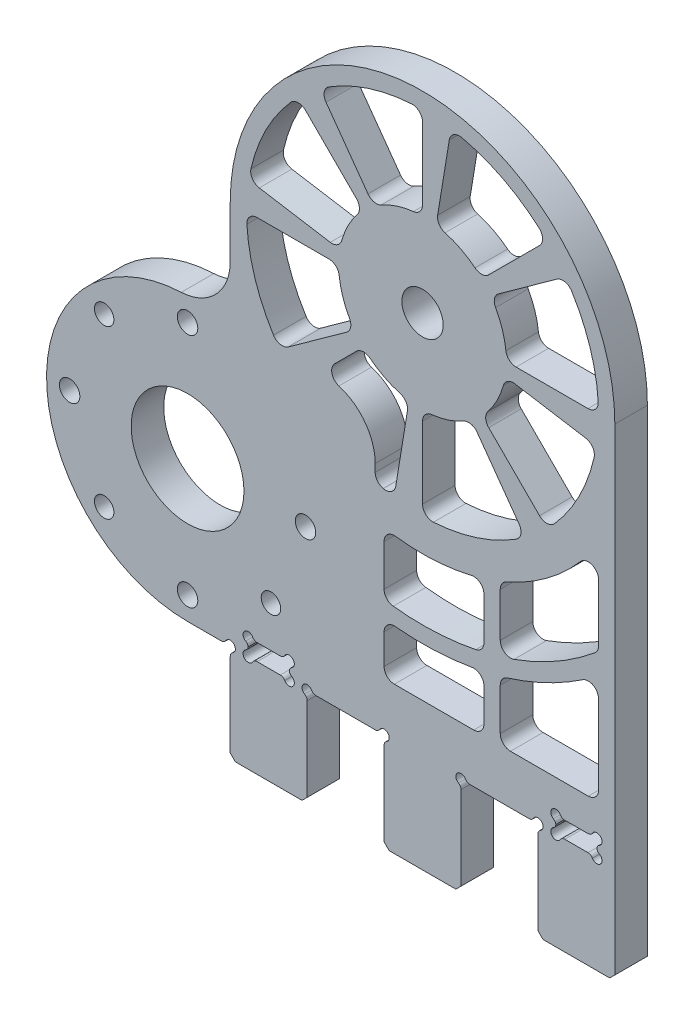
SolidWorks part; units mm, degrees
material "Balsa"
ref_plane "Front Plane" through (0, 0, 0) normal (0, 0, 1) x (1, 0, 0)
ref_plane "Top Plane" through (0, 0, 0) normal (0, 1, 0) x (1, 0, 0)
ref_plane "Right Plane" through (0, 0, 0) normal (1, 0, 0) x (0, 0, -1)
sketch "Sketch1" plane through (0, 0, 0) normal (0, 0, 1) x (1, 0, 0)
  line L0 (-56.9454, 94.4454) -> (-37.5, 75) construction
  line L1 (-40.4988, 0) -> (0, 0)
  line L2 (-75, 55) -> (-75, 75)
  line L3 (-40.4988, 0) -> (-83.323, 0)
  line L4 (0, 0) -> (0, 75)
  line L5 (-37.5, 75) -> (-65, 75) construction
  line L6 (-18.0546, 94.4454) -> (-37.5, 75) construction
  line L7 (-18.0546, 55.5546) -> (-37.5, 75) construction
  line L8 (-75, 55) -> (-83.323, 55)
  line L9 (-83.323, 27.5) -> (-83.323, 50.5) construction
  arc A0 (-75, 75) -> (0, 75) centre (-37.5, 75) cw
  arc A1 (-83.323, 55) -> (-83.323, 0) centre (-83.323, 27.5) ccw
  circle A2 centre (-83.323, 27.5) radius 11
  circle A3 centre (-37.5, 75) radius 4.03
  circle A4 centre (-83.323, 27.5) radius 23 construction
  circle A5 centre (-67.0596, 11.2365) radius 1.8987
  circle A6 centre (-83.323, 50.5) radius 1.9939
  circle A7 centre (-37.5, 75) radius 27.5 construction
  circle A8 centre (-37.5, 102.5) radius 1.8987 construction
  circle A9 centre (-10, 75) radius 1.8987 construction
  circle A10 centre (-37.5, 47.5) radius 1.8986 construction
  circle A11 centre (-65, 75) radius 1.8987 construction
  circle A12 centre (-56.9454, 94.4454) radius 1.5 construction
  circle A13 centre (-99.5865, 11.2365) radius 1.8987
  circle A14 centre (-60.323, 27.5) radius 1.9939
  circle A15 centre (-99.5865, 43.7635) radius 1.8987
  circle A16 centre (-83.323, 4.5) radius 1.9939
  circle A17 centre (-106.323, 27.5) radius 1.9939
  circle A19 centre (-18.0546, 94.4454) radius 1.5 construction
  circle A20 centre (-18.0546, 55.5546) radius 1.5 construction
  circle A21 centre (-56.9454, 55.5546) radius 1.5 construction
  circle A22 centre (-37.5, 75) radius 7.03 construction
  circle A23 centre (-37.5, 82.03) radius 1.75 construction
  circle A24 centre (-44.53, 75) radius 1.75 construction
  circle A25 centre (-37.5, 67.97) radius 1.75 construction
  circle A26 centre (-30.47, 75) radius 1.75 construction
  circle A28 centre (-67.0596, 43.7635) radius 1.8987 [skipped]
  point P0 (0, 0)
  point P63 (-83.323, 27.5)
  dimension "D3" = 27.5
  dimension "D5" = 8.06
  dimension "D6" = 22
  dimension "D7" = 46
  dimension "D8" = 3.7973
  dimension "D9" = 3.9878
  dimension "D11" = 55
  dimension "D13" = 3
  dimension "D16" = 3.5
  dimension "D17" = 3
  dimension "D1" = 75
  dimension "D2" = 66
  dimension "D4" = 75
  dimension "D10" = 4
  dimension "D14" = 45
  dimension "D12" = 4
  dimension "D15" = 4
extrude "Boss-Extrude1" add sketch "Sketch1" along normal blind 6.35
sketch "Sketch2" plane through (0, 0, 0) normal (0, 0, -1) x (-1, 0, 0)
  line L0 (83.323, 0) -> (0, 0) construction
  line L1 (0, 0) -> (15, 0)
  line L2 (0, 0) -> (0, -19.05)
  line L3 (0, -19.05) -> (15, -19.05)
  line L4 (15, 0) -> (15, -19.05)
  line L5 (30, 0) -> (45, 0)
  line L6 (30, 0) -> (30, -19.05)
  line L7 (30, -19.05) -> (45, -19.05)
  line L8 (45, 0) -> (45, -19.05)
  line L10 (60, 0) -> (75, 0)
  line L11 (60, 0) -> (60, -19.05)
  line L12 (60, -19.05) -> (75, -19.05)
  line L13 (75, 0) -> (75, -19.05)
  dimension "D1" = 15
  dimension "D2" = 15
  dimension "D3" = 19.05
  dimension "D4" = 15
extrude "Boss-Extrude2" add sketch "Sketch2" against normal up to surface (6.35 mm away) up to face at (-57.3577, 49.5833, 6.35)
chamfer "Chamfer1" distance 1 angle 45 6 edges at (0, -19.05, 3.175) (-15, -19.05, 3.175) (-30, -19.05, 3.175) (-45, -19.05, 3.175) (-60, -19.05, 3.175) (-75, -19.05, 3.175)
sketch "Sketch3" plane through (0, 0, 6.35) normal (0, 0, 1) x (1, 0, 0)
  line L0 (-83.323, 0) -> (-75, 0) construction
  circle A0 centre (-75, 0) radius 1
  circle A1 centre (-60, 0) radius 1
  circle A2 centre (-45, 0) radius 1
  circle A3 centre (-30, 0) radius 1
  circle A4 centre (-15, 0) radius 1
  dimension "D1" = 2
extrude "Cut-Extrude1" cut sketch "Sketch3" against normal through all
fillet "Fillet1" radius 10 1 edges at (-75, 55, 3.175)
other "Move Face1" [suppressed] offset 0.08 parameters "D1"=0.08
fillet "Fillet2" radius 1 10 edges at (-30, -1, 3.175) (-29, 0, 3.175) (-15, -1, 3.175) (-16, 0, 3.175) (-46, 0, 3.175) (-45, -1, 3.175) (-60, -1, 3.175) (-59, 0, 3.175) (-75, -1, 3.175) (-76, 0, 3.175)
sketch "Sketch4" plane through (0, 0, 6.35) normal (0, 0, 1) x (1, 0, 0)
  line L1 (-71.4967, 0) -> (-63.5033, 0)
  line L2 (-71.4967, 0) -> (-71.4967, 3.2207)
  line L3 (-71.4967, 3.2207) -> (-63.5033, 3.2207)
  line L4 (-63.5033, 0) -> (-63.5033, 3.2207)
  line L7 (-11.4967, 0) -> (-3.5033, 0)
  line L8 (-11.4967, 0) -> (-11.4967, 3.2207)
  line L9 (-11.4967, 3.2207) -> (-3.5033, 3.2207)
  line L10 (-3.5033, 0) -> (-3.5033, 3.2207)
  line L12 (-67.5, -19.05) -> (-67.5, 24.5659) construction
  line L13 (-74, -19.05) -> (-61, -19.05) construction
  line L14 (-7.5, -19.05) -> (-7.5, 11.2755) construction
  line L15 (-14, -19.05) -> (-1, -19.05) construction
  point P13 (-7.5, 0)
  point P14 (-63.5033, 1.6104)
  point P17 (-67.5, 0)
  dimension "D1" = 7.9934
  dimension "D2" = 7.9934
  dimension "D3" = 3.2207
  dimension "D6" = 3.2207
extrude "Cut-Extrude2" cut sketch "Sketch4" against normal through all
sketch "Sketch5" plane through (0, 0, 0) normal (0, 0, -1) x (-1, 0, 0)
  line L0 (84.5528, 54.9725) -> (46.7321, 54.9725) construction
  line L1 (46.7321, 54.9725) -> (46.7321, 0) construction
  line L2 (37.5, 112.5) -> (37.5, 75) construction
  line L3 (50.7784, 65.4603) -> (65.3766, 54.9725)
  line L4 (37.5, 75) -> (50.7784, 65.4603) construction
  line L5 (53.85, 75) -> (71.825, 75)
  line L6 (37.5, 75) -> (53.85, 75) construction
  arc A0 (75, 75) -> (0, 75) centre (37.5, 75) ccw construction
  circle A1 centre (37.5, 75) radius 16.35 construction
  circle A2 centre (37.5, 75) radius 34.325 construction
  arc A3 (50.7784, 65.4603) -> (53.85, 75) centre (37.5, 75) ccw
  arc A4 (65.3766, 54.9725) -> (71.825, 75) centre (37.5, 75) ccw
  dimension "D1" = 3.175
  dimension "D2" = 32.7
extrude "Cut-Extrude3" cut sketch "Sketch5" against normal through all
fillet "Fillet4" radius 2 4 edges at (-50.7784, 65.4603, 3.175) (-65.3766, 54.9725, 3.175) (-71.825, 75, 3.175) (-53.85, 75, 3.175)
pattern_circular "CirPattern1" count 8 over 360 about axis through (-37.5, 75, 6.35) along (0, 0, -1) of "Cut-Extrude3", "Fillet4"
sketch "Sketch7" plane through (0, 0, 0) normal (0, 0, -1) x (-1, 0, 0)
  line L0 (84.5528, 54.9725) -> (46.7321, 54.9725) construction
  line L1 (46.7321, 54.9725) -> (46.7321, 0) construction
  line L3 (56.7321, 54.9725) -> (72.323, 54.9725)
  line L4 (46.7321, 44.9725) -> (46.7321, 34.8057)
  line L5 (46.7321, 34.8057) -> (72.323, 34.8057)
  line L6 (72.323, 54.9725) -> (72.323, 34.8057)
  arc A0 (46.7321, 44.9725) -> (56.7321, 54.9725) centre (56.7321, 44.9725) cw
  point P11 (72.323, 34.8057)
  dimension "D1" = 10
extrude "Boss-Extrude3" add sketch "Sketch7" against normal through all
fillet "Fillet6" radius 2 2 edges at (-57.5275, 54.9725, 3.175) (-46.7321, 41.9398, 3.175)
sketch "Sketch8" plane through (0, 0, 6.35) normal (0, 0, 1) x (1, 0, 0)
  circle A0 centre (-71.4967, 3.2207) radius 1
  circle A1 centre (-63.5033, 3.2207) radius 1
  circle A2 centre (-63.5033, 0) radius 1
  circle A3 centre (-71.4967, 0) radius 1
  circle A4 centre (-11.4967, 3.2207) radius 1
  circle A5 centre (-3.5033, 3.2207) radius 1
  circle A6 centre (-3.5033, 0) radius 1
  circle A7 centre (-11.4967, 0) radius 1
  dimension "D1" = 2
extrude "Cut-Extrude4" cut sketch "Sketch8" against normal through all
fillet "Fillet8" radius 1 16 edges at (-10.4967, 0, 3.175) (-4.5033, 0, 3.175) (-3.5033, 1, 3.175) (-3.5033, 2.2207, 3.175) (-4.5033, 3.2207, 3.175) (-10.4967, 3.2207, 3.175) (-11.4967, 2.2207, 3.175) (-11.4967, 1, 3.175) (-71.4967, 2.2207, 3.175) (-71.4967, 1, 3.175) (-70.4967, 0, 3.175) (-64.5033, 0, 3.175) (-63.5033, 1, 3.175) (-63.5033, 2.2207, 3.175) (-64.5033, 3.2207, 3.175) (-70.4967, 3.2207, 3.175)
sketch "Sketch9" plane through (0, 0, 0) normal (0, 0, -1) x (-1, 0, 0)
  line L0 (45, 35.0224) -> (45, 9.5707) construction
  line L1 (45, 9.5707) -> (3.175, 9.5707) construction
  line L2 (3.175, 9.5707) -> (3.175, 53.1768) construction
  line L3 (45, -18.05) -> (45, -1.7321) construction
  line L4 (5.2354, 3.2207) -> (9.7646, 3.2207) construction
  line L5 (0, -18.05) -> (0, 75) construction
  line L6 (22.3476, 24.5444) -> (22.3476, 37.2527)
  line L7 (3.175, 9.5707) -> (45, 35.0224) construction
  line L8 (3.175, 35.0356) -> (3.175, 53.1768)
  line L9 (22.3476, 9.5707) -> (22.3476, 21.2378)
  line L11 (3.175, 30.9345) -> (3.175, 9.5707)
  line L12 (3.175, 9.5707) -> (22.3476, 9.5707)
  line L13 (25.5226, 9.5707) -> (25.5226, 20.4426)
  line L15 (45, 19.6491) -> (45, 9.5707)
  line L16 (45, 9.5707) -> (25.5226, 9.5707)
  line L17 (25.5226, 23.6979) -> (25.5226, 36.1285)
  line L19 (45, 22.8549) -> (45, 35.0224)
  line L20 (22.3476, 24.5444) -> (25.5226, 20.4426) construction
  circle A0 centre (37.5, 75) radius 4.03 construction
  circle A1 centre (37.5, 75) radius 4.03 construction
  arc A2 (3.175, 53.1768) -> (45, 35.0224) centre (37.5, 75) ccw construction
  arc A3 (8.4377, 93.2644) -> (3.2408, 77.1237) centre (37.5, 75) ccw construction
  arc A4 (3.175, 53.1768) -> (22.3476, 37.2527) centre (37.5, 75) ccw
  arc A5 (25.5226, 36.1285) -> (45, 35.0224) centre (37.5, 75) ccw
  arc A6 (3.175, 35.0356) -> (22.3476, 24.5444) centre (37.5, 75) ccw
  arc A7 (25.5226, 23.6979) -> (45, 22.8549) centre (37.5, 75) ccw
  arc A8 (3.175, 30.9345) -> (22.3476, 21.2378) centre (37.5, 75) ccw
  arc A9 (25.5226, 20.4426) -> (45, 19.6491) centre (37.5, 75) ccw
  point P0 (24.0875, 22.2966)
  dimension "D4" = 6.35
  dimension "D5" = 3.175
  dimension "D1" = 0
  dimension "D2" = 6.35
  dimension "D3" = 3.175
  dimension "D6" = 3.175
extrude "Cut-Extrude5" cut sketch "Sketch9" against normal through all
fillet "Fillet9" radius 2 16 edges at (-3.175, 9.5707, 3.175) (-22.3476, 9.5707, 3.175) (-22.3476, 21.2378, 3.175) (-3.175, 30.9345, 3.175) (-25.5226, 9.5707, 3.175) (-45, 9.5707, 3.175) (-45, 19.6491, 3.175) (-25.5226, 20.4426, 3.175) (-25.5226, 23.6979, 3.175) (-45, 22.8549, 3.175) (-45, 35.0224, 3.175) (-25.5226, 36.1285, 3.175) (-3.175, 35.0356, 3.175) (-22.3476, 24.5444, 3.175) (-22.3476, 37.2527, 3.175) (-3.175, 53.1768, 3.175)
